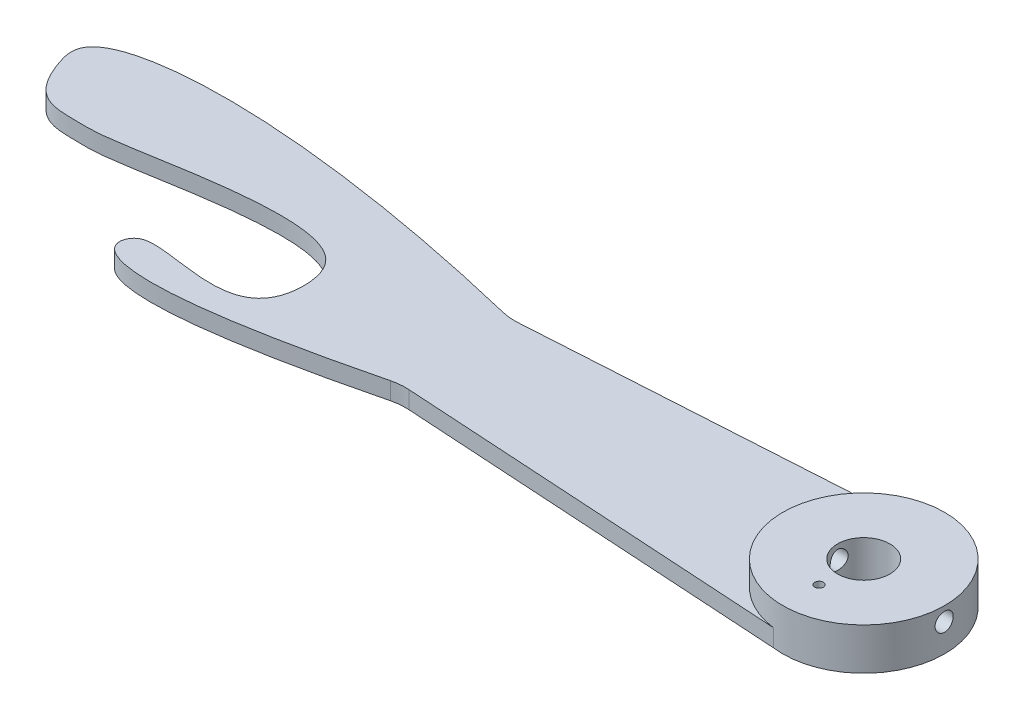
SolidWorks part; units mm, degrees
material "AISI 304"
ref_plane "Front Plane" through (0, 0, 0) normal (0, 0, 1) x (1, 0, 0)
ref_plane "Top Plane" through (0, 0, 0) normal (0, 1, 0) x (1, 0, 0)
ref_plane "Right Plane" through (0, 0, 0) normal (1, 0, 0) x (0, 0, -1)
sketch "Sketch1" plane through (0, 0, 0) normal (0, 1, 0) x (1, 0, 0)
  line L0 (-43.952, 17.8199) -> (-7.366, 20.066)
  line L1 (0, 0) -> (-91.44, 0)
  line L2 (0, 0) -> (0, 25.4)
  line L3 (0, 25.4) -> (-91.44, 25.4)
  line L4 (-91.44, 0) -> (-91.44, 25.4)
  line L5 (-43.6629, 7.5715) -> (-7.366, 5.334)
  circle A0 centre (-7.366, 12.7) radius 7.366
  circle A1 centre (-7.366, 12.7) radius 2.3813
  arc A2 (-43.952, 17.8199) -> (-45.4544, 17.952) centre (-44.2633, 22.8904) cw
  arc A3 (-45.2065, 7.4297) -> (-43.6629, 7.5715) centre (-43.9755, 2.5011) cw
  spline S0 degree 3 poles (-45.2065, 7.4297) (-68.7385, 1.5522) (-69.2549, 6.7433) (-65.4033, 8.1687) (-55.6776, 4.2553) (-57.3221, 18.1407) (-75.9393, 13.4655) (-81.607, 13.7017) (-84.3053, 13.4032) (-86.8829, 22.6761) (-69.3318, 23.7113) (-45.4544, 17.952) knots 0.001527 0.001527 0.001527 0.001527 0.145526 0.192265 0.438186 0.489915 0.657828 0.698156 0.852866 0.884868 0.998833 0.998833 0.998833 0.998833
  point P8 (-54.5064, 9.828)
  point P9 (-44.45, 12.7)
  point P10 (-51.3908, 8.4331)
  point P15 (-91.44, 12.7)
  point P19 (-65.7411, 10.3381)
  point P28 (-44.45, 7.62)
  dimension "D3" = 14.732
  dimension "D4" = 4.7625
  dimension "D6" = 5.08
  dimension "D13" = 5.08
  dimension "D1" = 25.4
  dimension "D2" = 91.44
  dimension "D5" = 0
  dimension "D7" = 0
  dimension "D8" = 44.45
  dimension "D9" = 0
  dimension "D10" = 5.08
extrude "Boss-Extrude1" add sketch "Sketch1" along normal blind 1.5875 contours S0 A3 L5 A0 L0 A2 | L5 A0 L0 A1 region at (-45.6014, 0, -13.8202) region at (-7.8037, 0, -19.8304)
sketch "Sketch2" plane through (0, 0, 0) normal (0, -1, 0) x (1, 0, 0)
  circle A0 centre (-7.366, -12.7) radius 2.3813
  circle A1 centre (-7.366, -12.7) radius 7.366
  dimension "D1" = 4.7625
  dimension "D2" = 14.732
extrude "Boss-Extrude2" add sketch "Sketch2" against normal blind 3.81
sketch "Sketch3" plane through (0, 0, 0) normal (1, 0, 0) x (0, 0, -1)
  line L0 (15.0812, 3.81) -> (10.3187, 3.81) construction
  line L2 (12.7, 3.81) -> (12.7, 2.54) construction
  circle A0 centre (12.7, 2.54) radius 0.8255
  dimension "D2" = 1.651
  dimension "D1" = 1.27
extrude "Cut-Extrude1" cut sketch "Sketch3" against normal through all
sketch "Sketch4" plane through (0, 3.81, 0) normal (0, 1, 0) x (1, 0, 0)
  line L1 (-7.366, 12.7) -> (-7.366, 8.636) construction
  circle A0 centre (-7.366, 8.636) radius 0.3937
  dimension "D1" = 0.7874
  dimension "D2" = 4.064
extrude "Cut-Extrude2" cut sketch "Sketch4" against normal up to next
